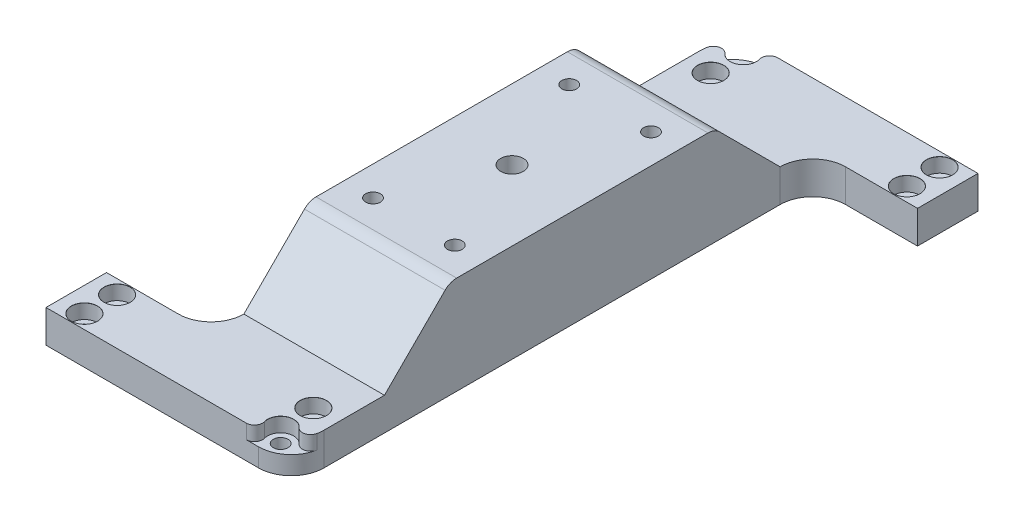
SolidWorks part; units mm, degrees
material "7075-T6 (SN)"
ref_plane "Front Plane" through (0, 0, 0) normal (0, 0, 1) x (1, 0, 0)
ref_plane "Top Plane" through (0, 0, 0) normal (0, 1, 0) x (1, 0, 0)
ref_plane "Right Plane" through (0, 0, 0) normal (1, 0, 0) x (0, 0, -1)
sketch "Sketch1" plane through (0, 0, 0) normal (0, 1, 0) x (1, 0, 0)
  line L0 (0, 0) -> (-21.5, 0) construction
  line L1 (-21.5, -89) -> (21.5, -89)
  line L2 (-21.5, -70.5) -> (-21.5, 89)
  line L5 (-21.5, -89) -> (21.5, 89) construction
  line L6 (-21.5, 89) -> (21.5, -89) construction
  line L7 (-53.5, -89) -> (-21.5, -89)
  line L8 (-53.5, -89) -> (-53.5, -70.5)
  line L9 (-53.5, -70.5) -> (-21.5, -70.5)
  line L11 (0, 0) -> (0, 89) construction
  line L12 (21.5, 70.5) -> (21.5, -89)
  line L13 (-21.5, 89) -> (53.5, 89)
  line L16 (53.5, 89) -> (53.5, 70.5)
  line L17 (53.5, 70.5) -> (21.5, 70.5)
  point P0 (0, 0)
  dimension "D1" = 18.5
  dimension "D2" = 43
  dimension "D3" = 32
  dimension "D4" = 32
  dimension "D5" = 18.5
extrude "Boss-Extrude1" add sketch "Sketch1" along normal blind 10
fillet "Fillet1" radius 10 4 edges at (-21.5, 5, -89) (21.5, 5, 89) (21.5, 5, -70.5) (-21.5, 5, 70.5)
sketch "Sketch2" plane through (0, 10, 0) normal (0, 1, 0) x (1, 0, 0)
  circle A0 centre (-14, 74.75) radius 1.75
  circle A1 centre (-14, 84.75) radius 1.75
  circle A2 centre (46, 74.75) radius 1.75
  circle A3 centre (46, 84.75) radius 1.75
  circle A4 centre (-46, -74.75) radius 1.75
  circle A5 centre (-46, -84.75) radius 1.75
  circle A6 centre (14, -74.75) radius 1.75
  circle A7 centre (14, -84.75) radius 1.75
extrude "Cut-Extrude1" cut sketch "Sketch2" against normal blind 10
hole_wizard "CBORE for M4 Hex Socket Head Cap Screw1" positions "Sketch3" profile "Sketch4" counterbore size "M4" standard "DIN"
sketch "Sketch3" plane through (0, 10, 0) normal (0, 1, 0) x (1, 0, 0)
  point P0 (-14, 74.75)
  point P3 (-14, 84.75)
  point P10 (46, 74.75)
  point P13 (14, -74.75)
  point P16 (14, -84.75)
  point P19 (-46, -84.75)
  point P22 (-46, -74.75)
  point P25 (46, 84.75)
sketch "Sketch4" plane through (-14, 10, -74.75) normal (1, 0, 0) x (0, 0, 1)
  line L0 (0, 0) -> (0, 11.3519)
  line L1 (0, 11.3519) -> (2.25, 10)
  line L2 (2.25, 10) -> (2.25, 4.4)
  line L3 (2.25, 4.4) -> (4, 4.4)
  line L5 (4, 4.4) -> (4, 0.025)
  line L6 (4, 0.025) -> (4.025, 0)
  line L7 (4.025, 0) -> (0, 0)
  line L8 (-4, 0.025) -> (-4.025, 0) construction
  line L10 (0, 11.3519) -> (-2.25, 10) construction
  line L11 (0, -6.35) -> (0, 107.95) construction
  dimension "Hole Dia." = 4.5
  dimension "Hole Depth" = 10
  dimension "C'Bore Dia." = 8
  dimension "C'Bore Depth" = 4.4
  dimension "Near C'Sink Dia." = 8.05
  dimension "Near C'Sink Angle" = 90
  dimension "Drill Angle" = 118
fillet "Fillet2" radius 2.5 2 edges at (-17.087, 7.7875, -87.2937) (-13.7548, 7.7875, -88.7425)
fillet "Fillet3" radius 2.5 2 edges at (13.7548, 7.7875, 88.7425) (17.087, 7.7875, 87.2937)
sketch "Sketch5" plane through (0, 10, 0) normal (0, 1, 0) x (1, 0, 0)
  line L1 (21.5, 60.5) -> (-21.5, 60.5)
  line L2 (21.5, 60.5) -> (21.5, -60.5)
  line L3 (21.5, -60.5) -> (-21.5, -60.5)
  line L4 (-21.5, 60.5) -> (-21.5, -60.5)
extrude "Boss-Extrude2" add sketch "Sketch5" along normal blind 20
chamfer "Chamfer1" distance 20 angle 45 2 edges at (0, 30, -60.5) (0, 30, 60.5)
sketch "Sketch6" plane through (0, 30, 0) normal (0, 1, 0) x (1, 0, 0)
  circle A0 centre (0, 0) radius 3.4625
extrude "Cut-Extrude2" cut sketch "Sketch6" against normal blind 20
sketch "Sketch7" plane through (0, 30, 0) normal (0, 1, 0) x (1, 0, 0)
  circle A0 centre (-12.5, 30) radius 2.25
  circle A1 centre (12.5, 30) radius 2.25
  circle A2 centre (12.5, -30) radius 2.25
  circle A3 centre (-12.5, -30) radius 2.25
  dimension "D1" = 4.5
extrude "Cut-Extrude3" cut sketch "Sketch7" against normal blind 20
fillet "Fillet4" radius 5 2 edges at (0, 30, 40.5) (0, 30, -40.5)
